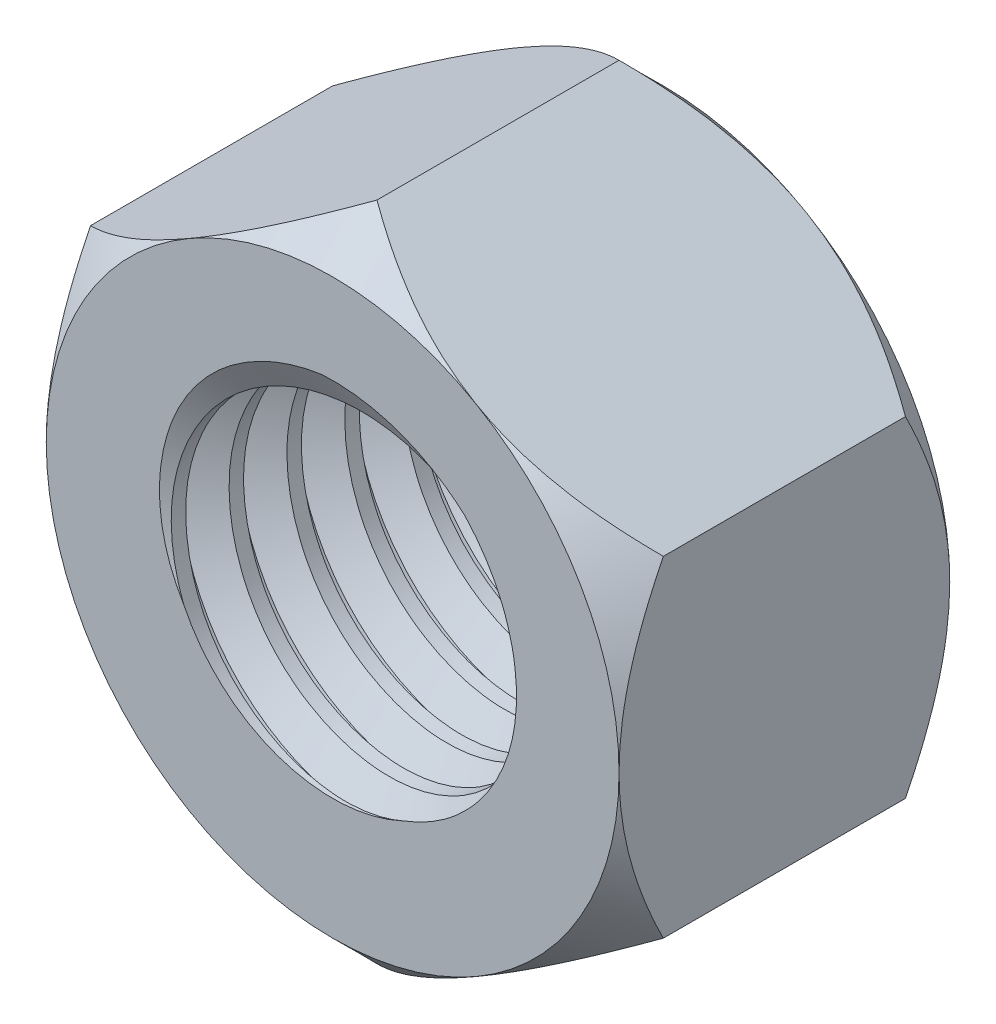
SolidWorks part; units mm, degrees
ref_plane "Front Plane" through (0, 0, 0) normal (0, 0, 1) x (1, 0, 0)
ref_plane "Top Plane" through (0, 0, 0) normal (0, 1, 0) x (1, 0, 0)
ref_plane "Right Plane" through (0, 0, 0) normal (1, 0, 0) x (0, 0, -1)
sketch "Sketch1" plane through (0, 0, 0) normal (0, 0, 1) x (1, 0, 0)
  line L1 (3.4641, 2) -> (0, 4)
  line L2 (0, 4) -> (-3.4641, 2)
  line L3 (-3.4641, 2) -> (-3.4641, -2)
  line L4 (-3.4641, -2) -> (0, -4)
  line L5 (0, -4) -> (3.4641, -2)
  line L6 (3.4641, -2) -> (3.4641, 2)
  circle A0 centre (0, 0) radius 3.4641 construction
  circle A1 centre (0, 0) radius 2
  dimension "D1" = 4
extrude "Boss-Extrude1" add sketch "Sketch1" along normal mid plane 4
thread "Thread2" pitch 0.7 method cut profile "Thread Profile2" start angle 0, offset 2, length 10, pitch 0.7, diameter 4
ref_plane "Plane2" through (2, 0, -4) normal (0, -1, 0) x (1, 0, 0)
sketch "Thread Profile2" plane through (2, 0, -4) normal (0, -1, 0) x (1, 0, 0)
  line L0 (0, 0) -> (0, 0.7) construction
  line L1 (0, 0) -> (0.3789, 0.2187)
  line L2 (0.3789, 0.2187) -> (0.3789, 0.3062)
  line L3 (0.3789, 0.3062) -> (0, 0.525)
  line L4 (0.3789, 0.2625) -> (0, 0.2625) construction
  line L11 (0, 0) -> (0, 0.525)
  point P2 (0, 0)
  dimension "Pitch" = 0.7
  dimension "Profile_Angle" = 60
  dimension "Profile_Land" = 0.0875
  dimension "Profile_Height" = 0.3789
sketch "Sketch9" plane through (0, 0, -2) normal (0, 0, -1) x (-1, 0, 0)
  circle A0 centre (0, 0) radius 3.4641
extrude "Cut-Extrude1" cut sketch "Sketch9" against normal blind 4 draft 45 flip side to cut
sketch "Sketch10" plane through (0, 0, 2) normal (0, 0, 1) x (1, 0, 0)
  circle A0 centre (0, 0) radius 3.4641
extrude "Cut-Extrude2" cut sketch "Sketch10" against normal blind 4 draft 45 flip side to cut
